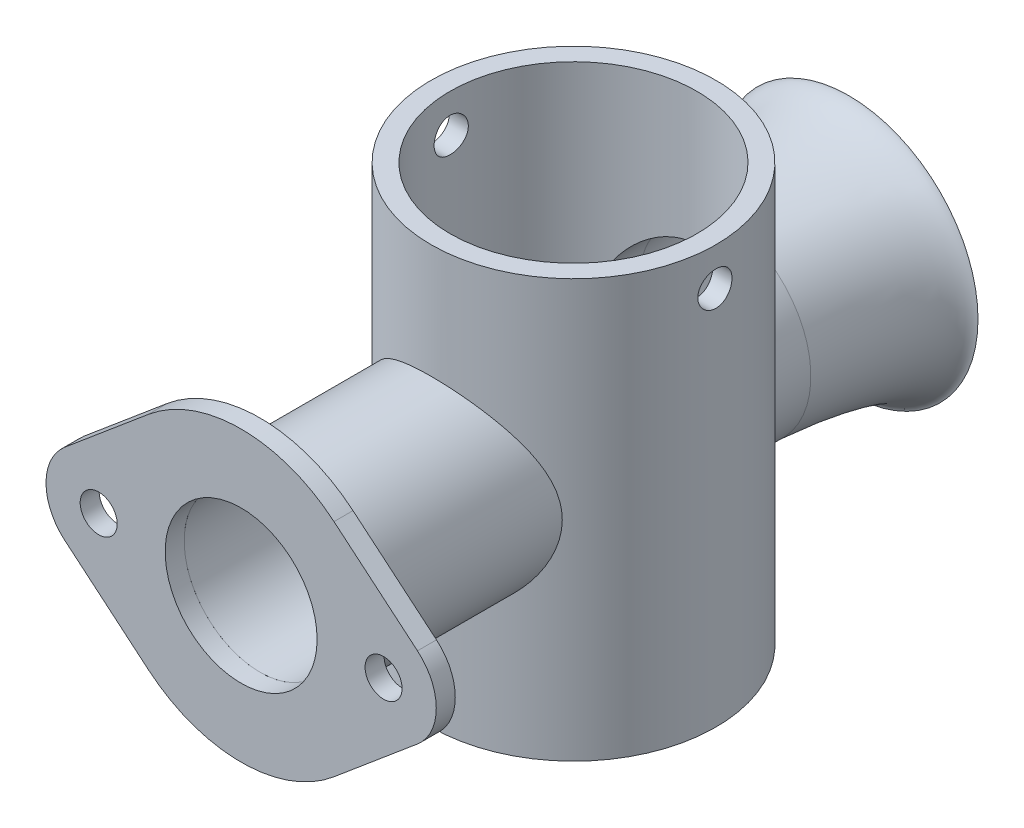
SolidWorks part; units mm, degrees
ref_plane "Front Plane" through (0, 0, 0) normal (0, 0, 1) x (1, 0, 0)
ref_plane "Top Plane" through (0, 0, 0) normal (0, 1, 0) x (1, 0, 0)
ref_plane "Right Plane" through (0, 0, 0) normal (1, 0, 0) x (0, 0, -1)
sketch "Sketch1" plane through (0, 0, 0) normal (0, 1, 0) x (1, 0, 0)
  circle A0 centre (0, 0) radius 7.5
  circle A1 centre (0, 0) radius 6.5
  dimension "D1" = 15
  dimension "D2" = 13
extrude "Boss-Extrude1" add sketch "Sketch1" along normal blind 22
sketch "Sketch2" plane through (0, 0, 0) normal (0, 0, 1) x (1, 0, 0)
  line L0 (-7.5, 22) -> (-7.5, 0) construction
  line L1 (7.5, 0) -> (7.5, 22) construction
  line L2 (-9.2852, 13.1245) -> (-4.8893, 16.8185)
  line L3 (0, 11) -> (0, 18.6) construction
  line L4 (9.2852, 13.1245) -> (4.8893, 16.8185)
  line L5 (-8.475, 11) -> (-6.525, 11) construction
  line L6 (-9.2852, 8.8755) -> (-4.8893, 5.1815)
  line L7 (9.2852, 8.8755) -> (4.8893, 5.1815)
  line L8 (6.525, 11) -> (7.5, 11) construction
  line L9 (-4.725, 11) -> (4.725, 11) construction
  circle A0 centre (0, 11) radius 4
  circle A1 centre (-7.5, 11) radius 0.975
  circle A2 centre (7.5, 11) radius 0.975
  arc A5 (9.2852, 8.8755) -> (9.2852, 13.1245) centre (7.5, 11) ccw
  arc A9 (4.8893, 16.8185) -> (-4.8893, 16.8185) centre (0, 11) ccw
  arc A11 (-4.8893, 5.1815) -> (4.8893, 5.1815) centre (0, 11) ccw
  arc A12 (-9.2852, 13.1245) -> (-9.2852, 8.8755) centre (-7.5, 11) ccw
  dimension "D1" = 8
  dimension "D2" = 1.95
  dimension "D3" = 1.95
  dimension "D5" = 5.55
extrude "Boss-Extrude2" add sketch "Sketch2" against normal blind 1 from offset 17.5 separate body
sketch "Sketch3" plane through (0, 0, 0) normal (0, 0, 1) x (1, 0, 0)
  circle A0 centre (0, 11) radius 5
  dimension "D1" = 10
extrude "Boss-Extrude3" add sketch "Sketch3" along normal up to surface (16.5 mm away) and the other way blind 7.5 separate body up to face at (8.475, 11, 16.5)
sketch "Sketch8" plane through (0, 0, 0) normal (1, 0, 0) x (0, 0, -1)
  line L0 (7.5, 11) -> (20.7109, 11) construction
  line L1 (7.5, 6) -> (7.5, 16) construction
  line L2 (14.5, 17.7993) -> (14.5, 16.7993)
  line L3 (7.5, 16) -> (7.5, 15)
  spline S0 degree 3 poles (7.5, 16) (10.0275, 16.146) (14.116, 16.7205) (14.5, 17.7993) knots 0 0 0 0 1 1 1 1
  spline S1 degree 3 poles (7.5, 15) (10.0275, 15.0708) (14.3269, 16.0973) (14.5, 16.7993) knots 0 0 0 0 1 1 1 1
  dimension "D1" = 1
  dimension "D2" = 1
  dimension "D3" = 7
revolve "Revolve1" add sketch "Sketch8" angle 360 about L0
sketch "Sketch9" plane through (0, 0, -7.5) normal (0, 0, -1) x (-1, 0, 0)
  circle A0 centre (0, 11) radius 4
extrude "Cut-Extrude1" cut sketch "Sketch9" against normal through all
sketch "Sketch11" plane through (0, 22, 0) normal (0, 1, 0) x (1, 0, 0)
  circle A0 centre (0, 0) radius 6.5 construction
  circle A1 centre (0, 0) radius 6.5
extrude "Boss-Extrude5" add sketch "Sketch11" against normal through all
sketch "Sketch12" plane through (0, 22, 0) normal (0, 1, 0) x (1, 0, 0)
  circle A0 centre (0, 0) radius 6.5
  dimension "D1" = 13
extrude "Cut-Extrude2" cut sketch "Sketch12" against normal blind 20
sketch "Sketch13" plane through (0, 0, 0) normal (0, -1, 0) x (1, 0, 0)
  circle A0 centre (0, 0) radius 1.5
  dimension "D1" = 3
extrude "Cut-Extrude3" cut sketch "Sketch13" against normal through all
sketch "Sketch14" plane through (0, 0, 0) normal (1, 0, 0) x (0, 0, -1)
  line L0 (6.5, 22) -> (-6.5, 22) construction
  line L1 (7.5, 16) -> (7.5, 22) construction
  circle A0 centre (0, 20) radius 0.9
  point P6 (1.1737, 18.971)
  dimension "D1" = 1.8
  dimension "D2" = 2
  dimension "D3" = 7.5
extrude "Cut-Extrude4" cut sketch "Sketch14" against normal through all both and the other way through all
